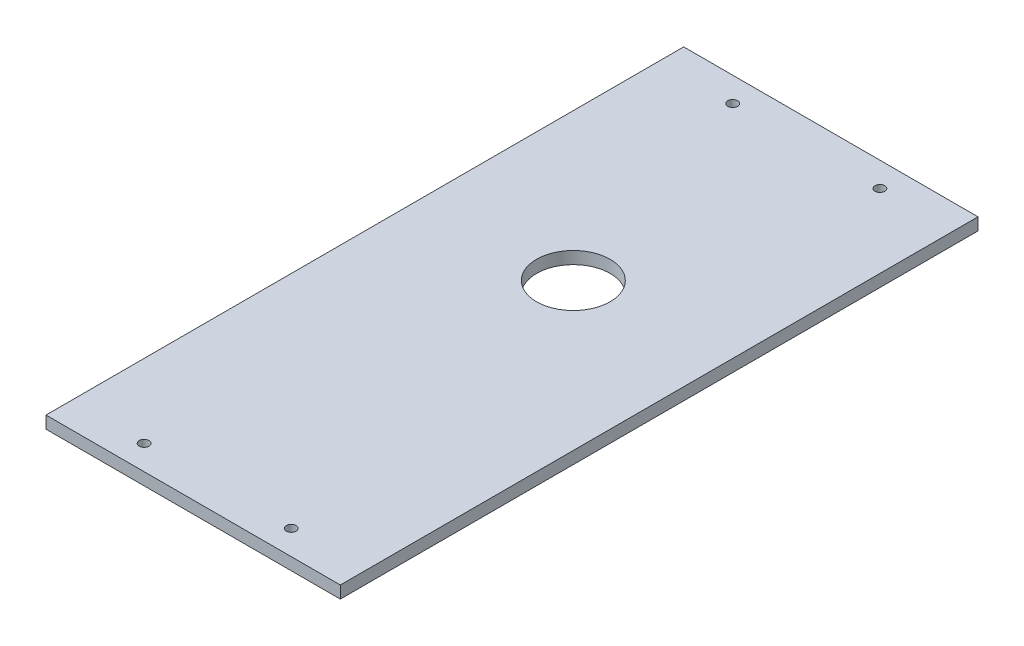
SolidWorks part; units mm, degrees
ref_plane "前视基准面" through (0, 0, 0) normal (0, 0, 1) x (1, 0, 0)
ref_plane "上视基准面" through (0, 0, 0) normal (0, 1, 0) x (1, 0, 0)
ref_plane "右视基准面" through (0, 0, 0) normal (1, 0, 0) x (0, 0, -1)
sketch "Sketch2" plane through (0, 0, 0) normal (0, 1, 0) x (1, 0, 0)
  line L1 (-60, 130) -> (60, 130)
  line L2 (-60, 130) -> (-60, -130)
  line L3 (-60, -130) -> (60, -130)
  line L4 (60, 130) -> (60, -130)
  line L5 (-60, 130) -> (60, -130) construction
  line L6 (-60, -130) -> (60, 130) construction
  point P0 (0, 0)
  dimension "D1" = 120
  dimension "D2" = 260
extrude "Boss-Extrude1" add sketch "Sketch2" along normal blind 5
sketch "Sketch3" plane through (0, 5, 0) normal (0, 1, 0) x (1, 0, 0)
  line L0 (60, -130) -> (60, 130) construction
  line L1 (-60, -130) -> (60, -130) construction
  circle A0 centre (0, 25) radius 15
  point P6 (24.2402, -116.5732)
  dimension "D1" = 30
  dimension "D3" = 155
  dimension "D2" = 60
extrude "Cut-Extrude1" cut sketch "Sketch3" against normal through all
sketch "Sketch5" plane through (0, 5, 0) normal (0, 1, 0) x (1, 0, 0)
  line L0 (-60, 0) -> (60, 0) construction
  line L1 (-60, 130) -> (-60, -130) construction
  line L2 (60, -130) -> (60, 130) construction
  line L3 (-60, 120) -> (60, 120) construction
  line L4 (60, 130) -> (-60, 130) construction
  line L5 (0, 0) -> (0, 130) construction
  circle A0 centre (-30, 120) radius 2
  circle A1 centre (30, 120) radius 2
  circle A2 centre (30, -120) radius 2
  circle A3 centre (-30, -120) radius 2
  dimension "D2" = 30
  dimension "D3" = 4
  dimension "D1" = 10
extrude "Cut-Extrude2" cut sketch "Sketch5" against normal through all
